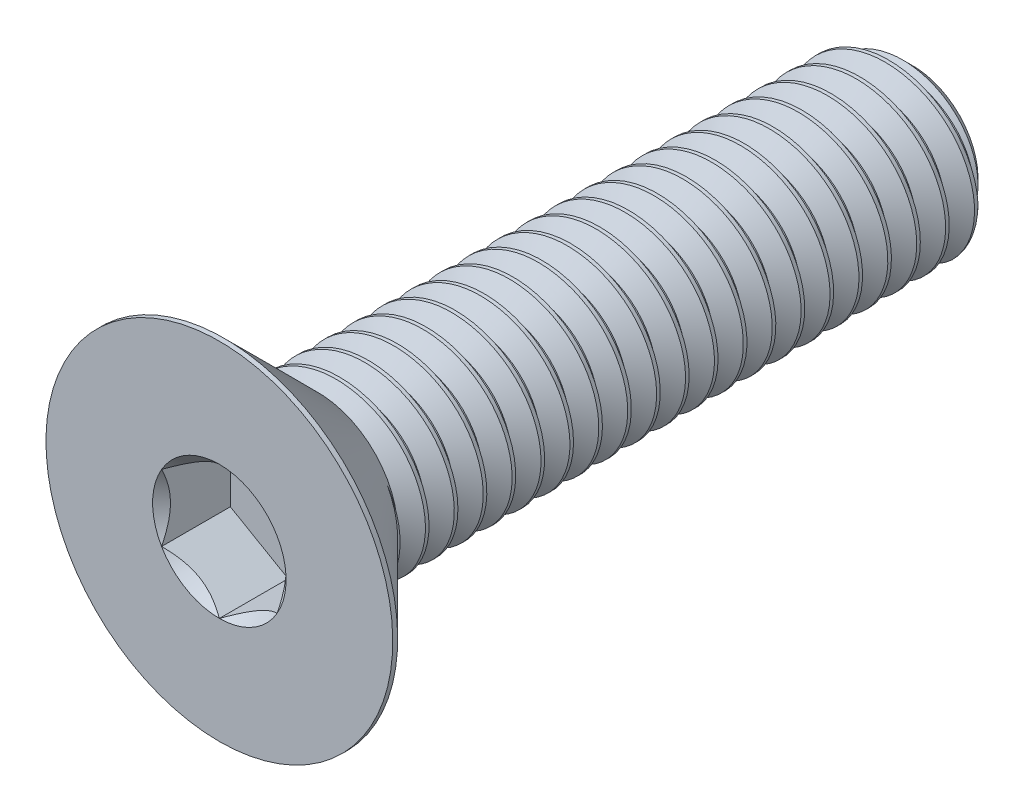
SolidWorks part; units mm, degrees
ref_plane "Front" through (0, 0, 0) normal (0, 0, 1) x (1, 0, 0)
ref_plane "Top" through (0, 0, 0) normal (0, 1, 0) x (1, 0, 0)
ref_plane "Right" through (0, 0, 0) normal (1, 0, 0) x (0, 0, -1)
sketch "Sketch11" plane through (0, 0, 0) normal (1, 0, 0) x (0, 0, -1)
  line L0 (-6, 3) -> (6, 3) construction
  line L5 (-6, 3) -> (-6, -3) construction
  line L6 (6, 1.5) -> (6, -1.5) construction
  line L7 (-5.99, 1) -> (-5.99, -1) construction
  line L8 (5.9688, 1.5541) -> (6.4688, 1.5541) construction
  line L9 (6.4688, 1.5541) -> (6.2188, 1.1211) construction
  line L10 (6.2188, 1.1211) -> (5.9688, 1.5541) construction
  line L11 (6.1875, 1.1752) -> (6.25, 1.1752) construction
  line L12 (6.2188, 1.1752) -> (6.2188, 1.1211) construction
  line L13 (5.9844, 1.5271) -> (6.4531, 1.5271) construction
  line L14 (6.2188, 1.5541) -> (6.2188, 1.5) construction
  line L15 (6, 1.5) -> (6.4375, 1.5) construction
  line L17 (-5.915, 3) -> (-2.915, 0) construction
  line L18 (-2.915, 0) -> (-5.915, -3) construction
  point P3 (-4.3, 3)
  point P8 (0, 3)
  point P21 (6.2188, 1.5271)
  point P26 (-6, 0)
  point P28 (-5.99, 0)
  point P29 (6, 0)
  dimension "Length" = 12
  dimension "Head Diameter" = 6
  dimension "Thread Major Diameter" = 3
  dimension "Head Height" = 1.7
  dimension "Drive Size" = 2
  dimension "Thread Pitch" = 0.5
  dimension "D1" = 0.0625
  dimension "D2" = 0.01
  dimension "D3" = 0.085
  dimension "Countersink Angle" = 90
sketch "Sketch1" plane through (0, 0, 0) normal (1, 0, 0) x (0, 0, -1)
  line L2 (-4.3, 1.5) -> (6, 1.5)
  line L3 (6, 1.5) -> (6, 0)
  line L4 (-4.81, 1.5) -> (-4.81, 0)
  line L5 (-4.3, 1.5) -> (-4.81, 1.5)
  line L6 (-6, 3) -> (-6, -3) construction
  line L7 (6, 1.5) -> (6, -1.5) construction
  line L8 (-4.81, 0) -> (6, 0)
  dimension "D1" = 1.19
revolve "Revolve1" add sketch "Sketch1" angle 360 mid plane about L8
chamfer "Chamfer1" distance 0.375 angle 45 1 edges at (0, -1.5, -6)
sketch "Sketch7" plane through (0, 0, 0) normal (1, 0, 0) x (0, 0, -1)
  line L2 (-6, 3) -> (-5.915, 3)
  line L5 (-4.3, 1.385) -> (-4.3, 0)
  line L6 (-6, 3) -> (-6, 0)
  line L8 (-6, 3) -> (-6, -3) construction
  line L9 (-6, 0) -> (-4.3, 0)
  line L12 (-5.915, 3) -> (-4.3, 1.385)
  line L13 (-5.915, 3) -> (-2.915, 0) construction
revolve "Revolve2" add sketch "Sketch7" angle 360 mid plane about L9 region at (0, 1.1696, 5.2571)
ref_plane "Plane1" through (0, 0, 4.3) normal (0, 0, 1) x (1, 0, 0)
sketch "Sketch5" plane through (0, 0, 6) normal (0, 0, 1) x (1, 0, 0)
  line L1 (1, -0.5774) -> (1, 0.5774)
  line L2 (1, 0.5774) -> (0, 1.1547)
  line L3 (0, 1.1547) -> (-1, 0.5774)
  line L4 (-1, 0.5774) -> (-1, -0.5774)
  line L5 (-1, -0.5774) -> (0, -1.1547)
  line L6 (0, -1.1547) -> (1, -0.5774)
  circle A0 centre (0, 0) radius 1 construction
extrude "Cut-Extrude2" cut sketch "Sketch5" against normal blind 1.19
sketch "Sketch6" plane through (0, 0, 6) normal (0, 0, -1) x (-1, 0, 0)
  circle A0 centre (0, 0) radius 1.1547
extrude "Cut-Extrude3" cut sketch "Sketch6" along normal blind 1.19 draft 45
sketch "Sketch12" plane through (0, 0, -6) normal (0, 0, -1) x (-1, 0, 0)
  circle A0 centre (0, 0) radius 1.5 construction
  circle A1 centre (0, 0) radius 1.5
curve "Helix/Spiral1" pitch 0.5 height 12 radius 1.5 centre (0, 0, -6) axis (0, 0, 1) start towards (0, 1, 0)
sketch "Sketch13" plane through (0, 0, 0) normal (1, 0, 0) x (0, 0, -1)
  line L0 (5.9844, 1.5271) -> (6.4531, 1.5271)
  line L1 (6.4531, 1.5271) -> (6.25, 1.1752)
  line L2 (6.25, 1.1752) -> (6.1875, 1.1752)
  line L3 (6.1875, 1.1752) -> (5.9844, 1.5271)
sweep "Cut-Sweep1" cut profiles "Sketch13" path "Helix/Spiral1" align with end faces yes
combine bodies "Combine1" operation type add bodies to combine 113 127
equation "\"D1@Chamfer1\"=\"Thread Pitch@Sketch11\" * .75"
equation "\"D1@Cut-Extrude2\"= \"Head Height@Sketch11\" * .7"
equation "\"D1@Cut-Extrude3\" = \"D1@Cut-Extrude2\""
equation "\"D1@Sketch11\"=\"Thread Pitch@Sketch11\"/8"
equation "\"D3@Sketch11\"=\"Head Height@Sketch11\"*.05"
equation "\"D4@Helix/Spiral1\"=\"Thread Pitch@Sketch11\""
equation "\"D1@Sketch1\"=\"Head Height@Sketch11\"*.7"
equation "\"D3@Helix/Spiral1\"=\"Length@Sketch11\""
